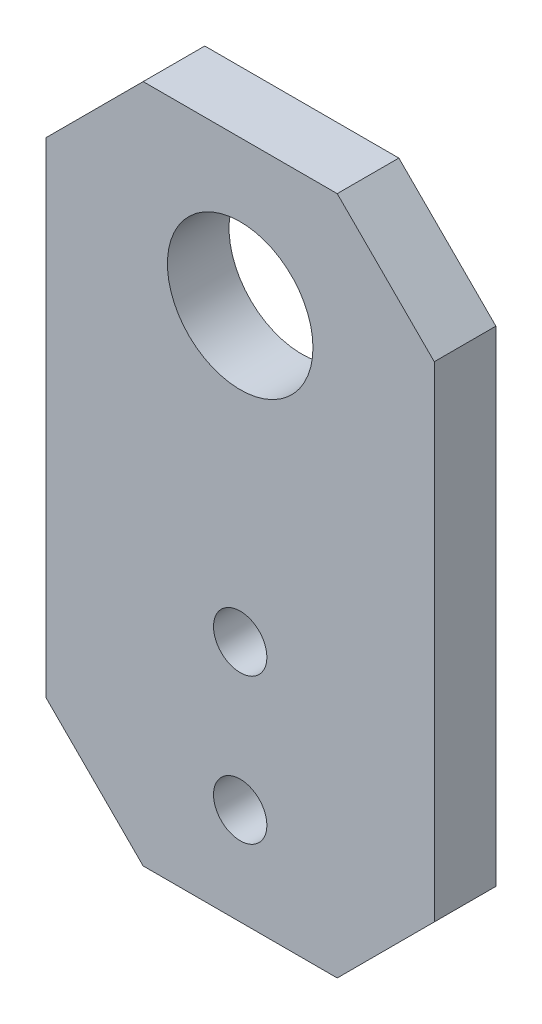
SolidWorks part; units mm, degrees
material "6061 Alloy"
ref_plane "Front Plane" through (0, 0, 0) normal (0, 0, 1) x (1, 0, 0)
ref_plane "Top Plane" through (0, 0, 0) normal (0, 1, 0) x (1, 0, 0)
ref_plane "Right Plane" through (0, 0, 0) normal (1, 0, 0) x (0, 0, -1)
sketch "Sketch1" plane through (0, 0, 0) normal (0, 0, 1) x (1, 0, 0)
  line L0 (0, 35) -> (0, -35) construction
  line L1 (-20, -35) -> (20, -35)
  line L2 (-20, -35) -> (-20, 35)
  line L3 (-20, 35) -> (20, 35)
  line L4 (20, -35) -> (20, 35)
  line L5 (-20, -35) -> (20, 35) construction
  line L6 (-20, 35) -> (20, -35) construction
  circle A0 centre (0, 20) radius 7.5
  circle A1 centre (0, -10) radius 2.5 construction
  circle A2 centre (0, -25) radius 2.5 construction
  point P4 (0, 0)
  dimension "D3" = 15
  dimension "D4" = 5
  dimension "D5" = 5
  dimension "D1" = 40
  dimension "D2" = 70
  dimension "D6" = 10
  dimension "D7" = 15
  dimension "D8" = 55
extrude "Boss-Extrude1" add sketch "Sketch1" along normal blind 6.35
hole_wizard "M5 Clearance Hole1" positions "Sketch4" profile "Sketch5" hole size "M5" standard "ISO" end condition through all
sketch "Sketch4" plane through (0, 0, 6.35) normal (0, 0, 1) x (1, 0, 0)
  point P0 (0, -10)
  point P3 (0, -25)
sketch "Sketch5" plane through (0, -10, 6.35) normal (1, 0, 0) x (0, -1, 0)
  line L0 (0, 0) -> (0, 6.35)
  line L1 (0, 6.35) -> (2.75, 6.35)
  line L2 (2.75, 6.35) -> (2.75, 0)
  line L5 (2.75, 0) -> (0, 0)
  line L11 (0, -6.35) -> (0, 107.95) construction
  dimension "Thru Hole Dia." = 5.5
  dimension "Thru Hole Depth" = 6.35
chamfer "Chamfer1" distance 10 angle 45 4 edges at (20, -35, 3.175) (-20, -35, 3.175) (20, 35, 3.175) (-20, 35, 3.175)
